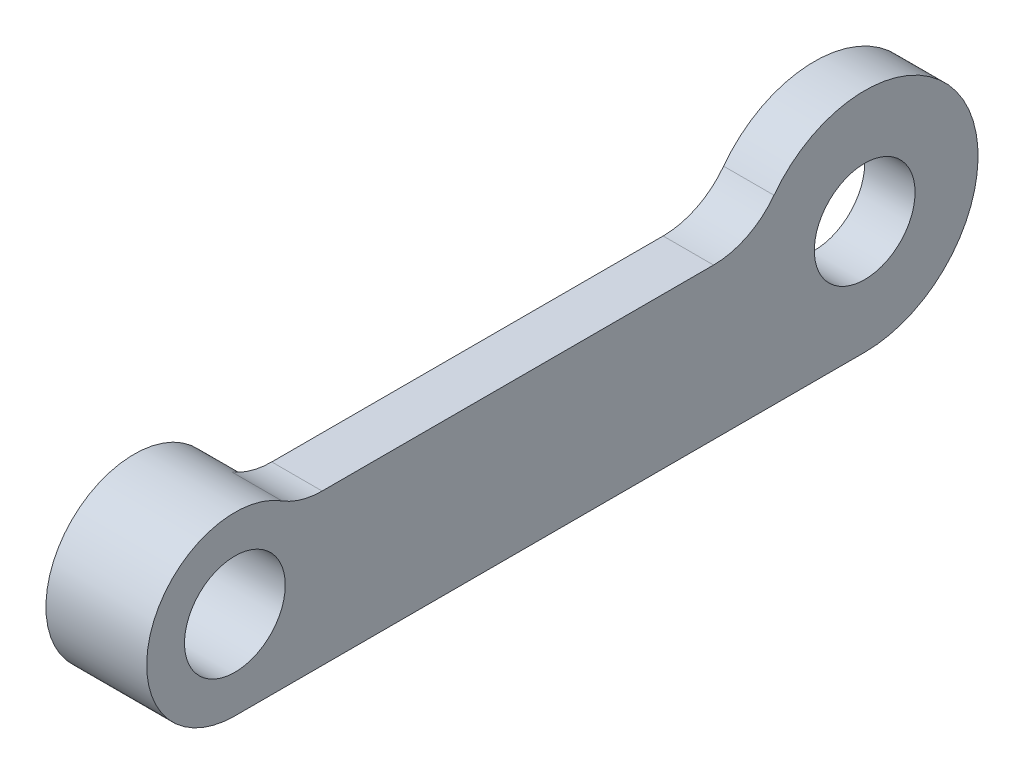
SolidWorks part; units mm, degrees
ref_plane "前视基准面" through (0, 0, 0) normal (0, 0, 1) x (1, 0, 0)
ref_plane "上视基准面" through (0, 0, 0) normal (0, 1, 0) x (1, 0, 0)
ref_plane "右视基准面" through (0, 0, 0) normal (1, 0, 0) x (0, 0, -1)
other "Configuration Table"
sketch "草图1" plane through (0, 0, 0) normal (1, 0, 0) x (0, 0, -1)
  line L1 (0, 0) -> (25, 0)
  line L2 (0, 0) -> (0, -6)
  line L3 (0, -6) -> (25, -6)
  line L4 (25, 0) -> (25, -6)
  circle A0 centre (0, -2.5) radius 3.5
  circle A1 centre (25, -1.5) radius 4.5
  circle A2 centre (0, -2.5) radius 2
  circle A3 centre (25, -1.5) radius 2
  dimension "D1" = 7
  dimension "D2" = 9
  dimension "D4" = 4
  dimension "D3" = 6
  dimension "D5" = 25
extrude "凸台-拉伸1" add sketch "草图1" along normal blind 2 contours A0 | L1 L4 L3 L2 | A1
extrude "凸台-拉伸3" add sketch "草图1<5>" against normal blind 2 contours A0
sketch "草图1<5>" plane through (0, 0, 0) normal (1, 0, 0) x (0, 0, -1) same geometry as "草图1"
extrude "切除-拉伸2" cut sketch "草图1<4>" along normal through all both and the other way through all contours L2 A2 | L2 A2 | L4 A3 L1 | L1 A3 L4 region at (0, -2.5, -0.8488) region at (0, -2.5, 0.8488) region at (0, -1.3854, -25.7577) region at (0, -1.6324, -24.1245)
sketch "草图1<4>" plane through (0, 0, 0) normal (1, 0, 0) x (0, 0, -1) same geometry as "草图1"
fillet "圆角1" radius 3 2 edges at (1, 0, -20.7574) (1, 0, -2.4495)
